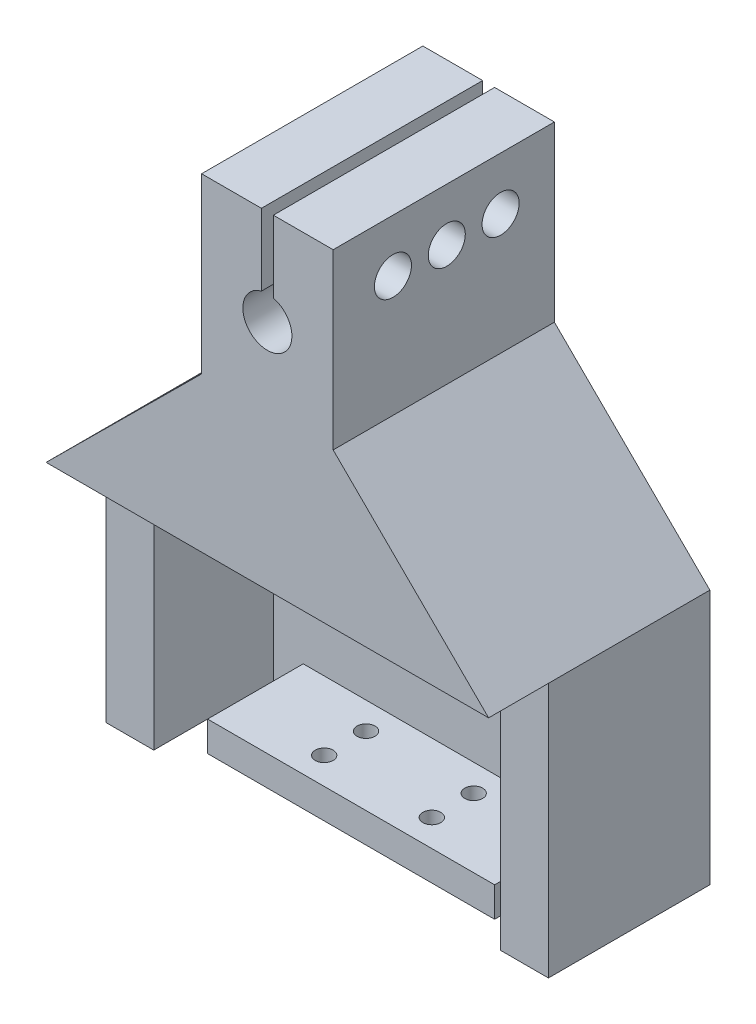
SolidWorks part; units mm, degrees
ref_plane "Alzado" through (0, 0, 0) normal (0, 0, 1) x (1, 0, 0)
ref_plane "Planta" through (0, 0, 0) normal (0, 1, 0) x (1, 0, 0)
ref_plane "Vista lateral" through (0, 0, 0) normal (1, 0, 0) x (0, 0, -1)
sketch "Croquis2" plane through (0, 0, 0) normal (0, 0, 1) x (1, 0, 0)
  line L0 (-30.7866, 48.816) -> (-5.7866, 48.816)
  line L1 (-5.7866, 48.816) -> (-5.7866, 40.816)
  line L2 (-5.7866, 40.816) -> (-30.7866, 40.816)
  line L3 (-30.7866, 48.816) -> (-30.7866, 40.816)
  line L5 (-22.5241, 25.0911) -> (-22.5241, 24.7943)
  line L7 (-18.1703, 25.0911) -> (-18.1703, 24.7943)
  line L8 (-5.7866, 48.816) -> (18.7134, 48.816)
  line L9 (-55.2866, 48.816) -> (-30.7866, 48.816)
  line L10 (18.7134, 48.816) -> (18.7134, 19.816)
  line L11 (-55.2866, 48.816) -> (-55.2866, 19.816)
  line L12 (-55.2866, 19.816) -> (-47.2866, 19.816)
  line L13 (-47.2866, 19.816) -> (-47.2866, 40.816)
  line L14 (-47.2866, 40.816) -> (-30.7866, 40.816)
  line L15 (18.7134, 19.816) -> (10.7134, 19.816)
  line L16 (10.7134, 19.816) -> (10.7134, 40.816)
  line L17 (10.7134, 40.816) -> (-5.7866, 40.816)
  line L18 (-55.2866, 19.816) -> (-55.2866, -5.184)
  line L19 (-55.2866, -5.184) -> (-47.2866, -5.184)
  line L20 (-47.2866, -5.184) -> (-47.2866, 19.816)
  line L21 (10.7134, 19.816) -> (10.7134, -5.184)
  line L22 (18.7134, 19.816) -> (18.7134, -5.184)
  line L23 (10.7134, -5.184) -> (18.7134, -5.184)
  line L24 (-55.2866, -5.184) -> (-55.2866, -30.184)
  line L25 (18.7134, -5.184) -> (18.7134, -30.184)
  line L26 (-47.2866, -5.184) -> (-47.2866, -30.184)
  line L27 (-31.9866, 6.2053) -> (-31.9866, -0.7947)
  line L28 (10.7134, -5.184) -> (10.7134, -30.184)
  line L29 (-55.2866, -30.184) -> (-47.2866, -30.184)
  line L30 (18.7134, -30.184) -> (10.7134, -30.184)
  line L31 (-55.2866, -30.184) -> (-55.2866, -49.184)
  line L32 (18.7134, -30.184) -> (18.7134, -49.184)
  line L34 (-47.2866, -30.184) -> (-47.2866, -49.184)
  line L35 (10.7134, -30.184) -> (10.7134, -49.184)
  line L36 (-47.2866, -49.184) -> (-55.2866, -49.184)
  line L37 (10.7134, -49.184) -> (18.7134, -49.184)
  line L38 (-40.2866, -56.184) -> (-30.7866, -56.184)
  line L39 (3.7134, -56.184) -> (3.7134, -64.184)
  line L40 (-30.7866, -56.184) -> (-30.7866, -64.184)
  line L41 (-19.2866, 103.616) -> (-29.2866, 103.616)
  line L42 (-30.7866, -64.184) -> (-40.2866, -64.184)
  line L43 (-30.7866, -56.184) -> (-5.7866, -56.184)
  line L44 (-40.2866, -64.184) -> (-40.2866, -56.184)
  line L45 (-5.7866, -56.184) -> (-5.7866, -64.184)
  line L46 (-5.7866, -64.184) -> (-30.7866, -64.184)
  line L47 (3.7134, -64.184) -> (-5.7866, -64.184)
  line L48 (-5.7866, -56.184) -> (3.7134, -56.184)
  line L49 (-4.5866, 30.2053) -> (-4.5866, 37.2053)
  line L50 (-7.2866, 21.7053) -> (-7.2866, 14.7053)
  line L51 (-0.9866, 30.2053) -> (-0.9866, 37.2053)
  line L52 (-29.2866, 21.7053) -> (-29.2866, 14.7053)
  line L53 (-0.9866, 6.2053) -> (-0.9866, -0.7947)
  line L54 (-4.5866, 6.2053) -> (-4.5866, -0.7947)
  line L55 (-35.5866, 6.2053) -> (-35.5866, -0.7947)
  line L56 (-35.5866, 30.2053) -> (-35.5866, 37.2053)
  line L57 (-31.9866, 30.2053) -> (-31.9866, 37.2053)
  line L58 (-17.2866, 103.616) -> (-7.2866, 103.616)
  line L59 (-55.2866, 48.816) -> (-29.2866, 74.616)
  line L63 (-29.2866, 103.616) -> (-29.2866, 74.616)
  line L64 (-19.2866, 103.616) -> (-19.2866, 91.616)
  line L65 (18.7134, 48.816) -> (-7.2866, 74.616)
  line L66 (-17.2866, 103.616) -> (-17.2866, 91.616)
  line L67 (-7.2866, 103.616) -> (-7.2866, 74.616)
  arc A0 (-55.2866, -49.184) -> (-40.2866, -64.184) centre (-40.2866, -49.184) ccw
  arc A1 (18.7134, -49.184) -> (3.7134, -64.184) centre (3.7134, -49.184) cw
  arc A2 (-47.2866, -49.184) -> (-40.2866, -56.184) centre (-40.2866, -49.184) ccw
  arc A3 (3.7134, -56.184) -> (10.7134, -49.184) centre (3.7134, -49.184) ccw
  circle A4 centre (-18.2866, -27.184) radius 9
  arc A5 (-7.2866, 21.7053) -> (-29.2866, 21.7053) centre (-18.2866, 21.7053) ccw
  arc A7 (-29.2866, 14.7053) -> (-7.2866, 14.7053) centre (-18.2866, 14.7053) ccw
  arc A8 (-0.9866, 37.2053) -> (-4.5866, 37.2053) centre (-2.7866, 37.2053) ccw
  arc A9 (-4.5866, 30.2053) -> (-0.9866, 30.2053) centre (-2.7866, 30.2053) ccw
  arc A10 (-4.5866, 6.2053) -> (-0.9866, 6.2053) centre (-2.7866, 6.2053) cw
  arc A11 (-0.9866, -0.7947) -> (-4.5866, -0.7947) centre (-2.7866, -0.7947) cw
  arc A12 (-35.5866, -0.7947) -> (-31.9866, -0.7947) centre (-33.7866, -0.7947) ccw
  arc A13 (-31.9866, 6.2053) -> (-35.5866, 6.2053) centre (-33.7866, 6.2053) ccw
  arc A14 (-31.9866, 30.2053) -> (-35.5866, 30.2053) centre (-33.7866, 30.2053) cw
  arc A15 (-35.5866, 37.2053) -> (-31.9866, 37.2053) centre (-33.7866, 37.2053) cw
  arc A16 (-19.2866, 91.616) -> (-17.2866, 91.616) centre (-18.2866, 87.6398) ccw
extrude "Saliente-Extruir1" add sketch "Croquis2" along normal blind 7 contours L48 A3 L35 L28 L21 L16 L17 L2 L14 L13 L20 L26 L34 A2 L38 L43 A13 L27 A12 L55 A9 L49 A8 L51 A7 L52 A5 L50 A4 L53 A11 L54 A10 L56 A15 L57 A14 | A15 L56 A14 L57 | L27 A13 L55 A12 | A4 | L52 A7 L50 A5 | L49 A9 L51 A8 | L53 A11 L54 A10 region at (-18.2866, -10.1531, 0) region at (-33.7866, 2.7053, 0) region at (-2.7866, 33.7053, 0) region at (-18.2866, 18.2053, 0) region at (-33.7866, 33.7053, 0) region at (-18.2866, -27.184, 0)
extrude "Saliente-Extruir3" add sketch "Croquis2<7>" along normal blind 27 contours L21 L23 L22 L15 | L17 L16 L15 L10 L8 L1 | L0 L3 L2 L1 | L13 L14 L3 L9 L11 L12 | L19 L20 L12 L18 region at (-18.2866, 44.816, 0) region at (-31.1663, 44.816, 0) region at (6.4634, 48.4364, 0) region at (-51.2866, 7.316, 0) region at (14.7134, 7.316, 0)
sketch "Croquis2<7>" plane through (0, 0, 0) normal (0, 0, 1) x (1, 0, 0) same geometry as "Croquis2"
extrude "Saliente-Extruir5" add sketch "Croquis2<14>" along normal blind 37 contours A16 L64 L41 L63 L59 L9 L0 L8 L65 L67 L58 L66 region at (-18.2866, 68.5898, 0)
sketch "Croquis2<14>" plane through (0, 0, 0) normal (0, 0, 1) x (1, 0, 0) same geometry as "Croquis2"
sketch "Croquis10" plane through (-7.2866, 0, 0) normal (1, 0, 0) x (0, 0, -1)
  circle A0 centre (-9, 94.816) radius 1.9
  circle A1 centre (-18, 94.816) radius 1.9
  circle A2 centre (-27, 94.816) radius 1.9
extrude "Cortar-Extruir3" cut sketch "Croquis10" against normal blind 22
sketch "Croquis11" plane through (-7.2866, 0, 0) normal (1, 0, 0) x (0, 0, -1)
  circle A0 centre (-27, 94.816) radius 3.1
  circle A1 centre (-18, 94.816) radius 3.1
  circle A2 centre (-9, 94.816) radius 3.1
extrude "Cortar-Extruir4" cut sketch "Croquis11" against normal blind 6
sketch "Croquis12" plane through (-29.2866, 0, 0) normal (-1, 0, 0) x (0, 0, 1)
  line L7 (21.2332, 94.816) -> (19.6166, 97.616)
  line L8 (19.6166, 97.616) -> (16.3834, 97.616)
  line L9 (16.3834, 97.616) -> (14.7668, 94.816)
  line L10 (14.7668, 94.816) -> (16.3834, 92.016)
  line L11 (16.3834, 92.016) -> (19.6166, 92.016)
  line L12 (19.6166, 92.016) -> (21.2332, 94.816)
  line L13 (12.2332, 94.816) -> (10.6166, 97.616)
  line L14 (10.6166, 97.616) -> (7.3834, 97.616)
  line L15 (7.3834, 97.616) -> (5.7668, 94.816)
  line L16 (5.7668, 94.816) -> (7.3834, 92.016)
  line L17 (7.3834, 92.016) -> (10.6166, 92.016)
  line L18 (10.6166, 92.016) -> (12.2332, 94.816)
  line L25 (30.2332, 94.816) -> (28.6166, 97.616)
  line L26 (28.6166, 97.616) -> (25.3834, 97.616)
  line L27 (25.3834, 97.616) -> (23.7668, 94.816)
  line L28 (23.7668, 94.816) -> (25.3834, 92.016)
  line L29 (25.3834, 92.016) -> (28.6166, 92.016)
  line L30 (28.6166, 92.016) -> (30.2332, 94.816)
  circle A0 centre (9, 94.816) radius 2.8 construction
  circle A1 centre (18, 94.816) radius 2.8 construction
  circle A2 centre (27, 94.816) radius 2.8 construction
extrude "Cortar-Extruir5" cut sketch "Croquis12" against normal blind 6
sketch "Croquis16" plane through (0, 0, 7) normal (0, 0, 1) x (1, 0, 0)
  line L0 (-18.2866, 87.6398) -> (-18.2866, -12.3602)
  line L3 (-47.2866, -12.3602) -> (10.7134, -12.3602)
  line L4 (-47.2866, -12.3602) -> (-47.2866, 40.816)
  line L5 (-47.2866, 40.816) -> (10.7134, 40.816)
  line L6 (10.7134, -12.3602) -> (10.7134, 40.816)
  line L7 (-47.2866, -12.3602) -> (10.7134, 40.816) construction
  line L8 (-47.2866, 40.816) -> (10.7134, -12.3602) construction
  point P0 (-18.2866, 14.2279)
sketch "Croquis17" plane through (0, 0, 7) normal (0, 0, 1) x (1, 0, 0)
  line L0 (-18.2866, -12.3602) -> (-18.2866, 6.1398)
  line L1 (-18.2866, 87.6398) -> (-18.2866, -12.3602) construction
  line L2 (-18.2866, 6.1398) -> (-18.2866, 2.6398)
  line L3 (-42.2866, 6.1398) -> (-55.2866, 6.1398)
  line L4 (-42.2866, 6.1398) -> (5.7134, 6.1398)
  line L5 (-42.2866, 6.1398) -> (-42.2866, -0.8602)
  line L6 (-42.2866, -0.8602) -> (5.7134, -0.8602)
  line L7 (5.7134, 6.1398) -> (5.7134, -0.8602)
  line L8 (-42.2866, 6.1398) -> (5.7134, -0.8602) construction
  line L9 (-42.2866, -0.8602) -> (5.7134, 6.1398) construction
  line L10 (-42.2866, 6.1398) -> (5.7134, 6.1398)
  line L11 (-42.2866, 6.1398) -> (-42.2866, 11.1398)
  line L12 (-42.2866, 11.1398) -> (5.7134, 11.1398)
  line L13 (5.7134, 6.1398) -> (5.7134, 11.1398)
  line L14 (-55.2866, 48.816) -> (-55.2866, -5.184) construction
  line L15 (-55.2866, 6.1398) -> (-55.2866, -5.184)
  line L16 (-55.2866, -5.184) -> (10.7134, -5.184)
  line L17 (10.7134, -5.184) -> (18.7134, -5.184)
  line L18 (18.7134, -5.184) -> (18.7134, 6.1398)
  line L19 (18.7134, 48.816) -> (18.7134, -5.184) construction
  line L20 (18.7134, 6.1398) -> (10.7134, 6.1398)
  line L21 (10.7134, -12.3602) -> (10.7134, 40.816) construction
  line L22 (10.7134, 6.1398) -> (10.7134, -5.184)
  line L23 (-47.2866, -5.184) -> (-47.2866, 6.1398)
  line L24 (-47.2866, -12.3602) -> (-47.2866, 40.816) construction
  line L25 (10.7134, 6.1398) -> (5.7134, 6.1398)
  line M9 (-47.2866, 40.816) -> (-47.2866, -5.184)
  line M14 (-40.2866, -56.184) -> (3.7134, -56.184)
  arc M15 (3.7134, -56.184) -> (10.7134, -49.184) centre (3.7134, -49.184) ccw
  line M16 (10.7134, -49.184) -> (10.7134, -5.184)
  line M17 (10.7134, -5.184) -> (10.7134, 40.816)
  line M18 (-47.2866, -5.184) -> (-47.2866, -49.184)
  arc M19 (-47.2866, -49.184) -> (-40.2866, -56.184) centre (-40.2866, -49.184) ccw
  dimension "D1" = 18.5
  dimension "D2" = 7
  dimension "D3" = 48
  dimension "D4" = 5
extrude "Cortar-Extruir6" cut sketch "Croquis17" against normal blind 7 contours L16 M18 M19 M14 M15 M16 | L16 L0 L6 L5 L3 M9 | L25 L7 L6 L0 L16 M17 | L7 L4 L0 L6 | L5 L6 L0 L4 | L15 L16 L3 M9 | L18 L20 L17 M17 region at (-30.2866, 2.6398, 7) region at (-6.2866, 2.6398, 7) region at (-1.168, -1.7866, 7) region at (-35.4052, -1.7866, 7) region at (-18.2866, -30.5126, 7) region at (-51.2866, 0.4779, 7) region at (14.7134, 0.4779, 7)
extrude "Cortar-Extruir7" cut sketch "Croquis17<4>" along normal blind 20 contours L15 L16 L3 M9 | L18 L20 L17 M17 region at (-51.2866, 0.4779, 7) region at (14.7134, 0.4779, 7)
sketch "Croquis17<4>" plane through (0, 0, 7) normal (0, 0, 1) x (1, 0, 0) same geometry as "Croquis17"
extrude "Saliente-Extruir6" add sketch "Croquis17<5>" along normal blind 16 contours L4 L13 L12 L11 region at (-18.2866, 8.6398, 7)
sketch "Croquis17<5>" plane through (0, 0, 7) normal (0, 0, 1) x (1, 0, 0) same geometry as "Croquis17"
sketch "Croquis18" plane through (0, 6.1398, 0) normal (0, -1, 0) x (1, 0, 0)
  line L0 (-18.2866, 23) -> (-18.2866, 7)
  line L1 (-42.2866, 23) -> (5.7134, 23)
  line L2 (-42.2866, 23) -> (-42.2866, 7)
  line L3 (-42.2866, 7) -> (5.7134, 7)
  line L4 (5.7134, 23) -> (5.7134, 7)
  line L10 (-27.2866, 11.5) -> (-9.2866, 11.5)
  line L11 (-27.2866, 11.5) -> (-27.2866, 18.5)
  line L12 (-27.2866, 18.5) -> (-9.2866, 18.5)
  line L13 (-9.2866, 11.5) -> (-9.2866, 18.5)
  line L14 (-27.2866, 11.5) -> (-9.2866, 18.5) construction
  line L15 (-27.2866, 18.5) -> (-9.2866, 11.5) construction
  circle A0 centre (-27.2866, 18.5) radius 1.5
  circle A1 centre (-27.2866, 11.5) radius 1.5
  circle A2 centre (-9.2866, 18.5) radius 1.5
  circle A3 centre (-9.2866, 11.5) radius 1.5
  point P8 (-18.2866, 15)
  dimension "D1" = 18
  dimension "D2" = 7
extrude "Cortar-Extruir8" cut sketch "Croquis18" against normal blind 10 contours L12 A0 L11 | L13 A2 L12 | L10 A3 L13 | L11 A1 L10 | L11 A0 L12 | L10 A1 L11 | L13 A3 L10 | L12 A2 L13 region at (-26.65, 6.1398, 17.8634) region at (-27.4988, 6.1398, 18.7122) region at (-9.0744, 6.1398, 18.7122) region at (-9.9232, 6.1398, 17.8634) region at (-27.4988, 6.1398, 11.2878) region at (-26.65, 6.1398, 12.1366) region at (-9.9232, 6.1398, 12.1366) region at (-9.0744, 6.1398, 11.2878)
